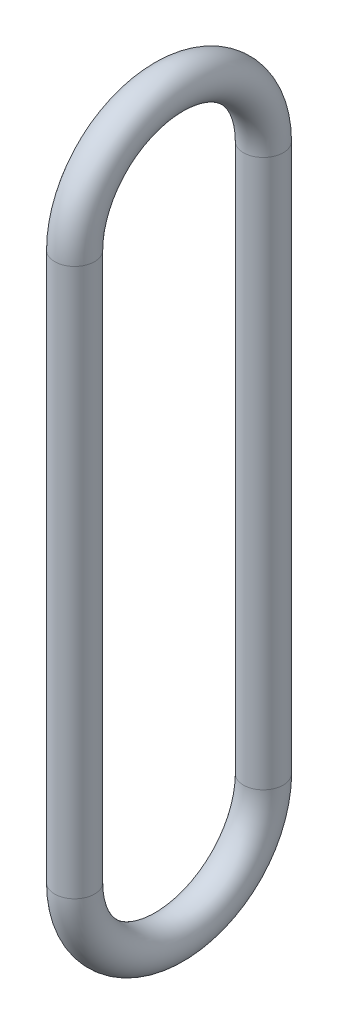
SolidWorks part; units mm, degrees
material "Rubber"
ref_plane "Front Plane" through (0, 0, 0) normal (0, 0, 1) x (1, 0, 0)
ref_plane "Top Plane" through (0, 0, 0) normal (0, 1, 0) x (1, 0, 0)
ref_plane "Right Plane" through (0, 0, 0) normal (1, 0, 0) x (0, 0, -1)
sketch "Sketch2" plane through (0, 0, 0) normal (0, 1, 0) x (1, 0, 0)
  circle A0 centre (0, 0) radius 6.35
  dimension "D1" = 12.7
sketch "Sketch3" plane through (0, 0, 0) normal (1, 0, 0) x (0, 0, -1)
  line L0 (0, 0) -> (0, 175.0238)
  line L1 (-60.325, 175.0238) -> (-60.325, 0)
  arc A0 (0, 175.0238) -> (-60.325, 175.0238) centre (-30.1625, 175.0238) ccw
  arc A1 (0, 0) -> (-60.325, 0) centre (-30.1625, 0) cw
  dimension "D1" = 30.1625
  dimension "D2" = 175.0238
sweep "Sweep1" add profiles "Sketch2" path "Sketch3"
ref_plane "Plane1" through (0, 0, 0) normal (0, 1, 0) x (1, 0, 0)
ref_plane "Plane2" through (0, 0, 30.1625) normal (0, 0, 1) x (1, 0, 0)
ref_axis "Axis1" through (-7.1192, 0, 30.1625) along (1, 0, 0)
ref_plane "Plane3" through (0, 175.0238, 0) normal (0, -1, 0) x (-1, 0, 0)
ref_axis "Axis2" through (-7.1193, 175.0238, 30.1625) along (1, 0, 0)
